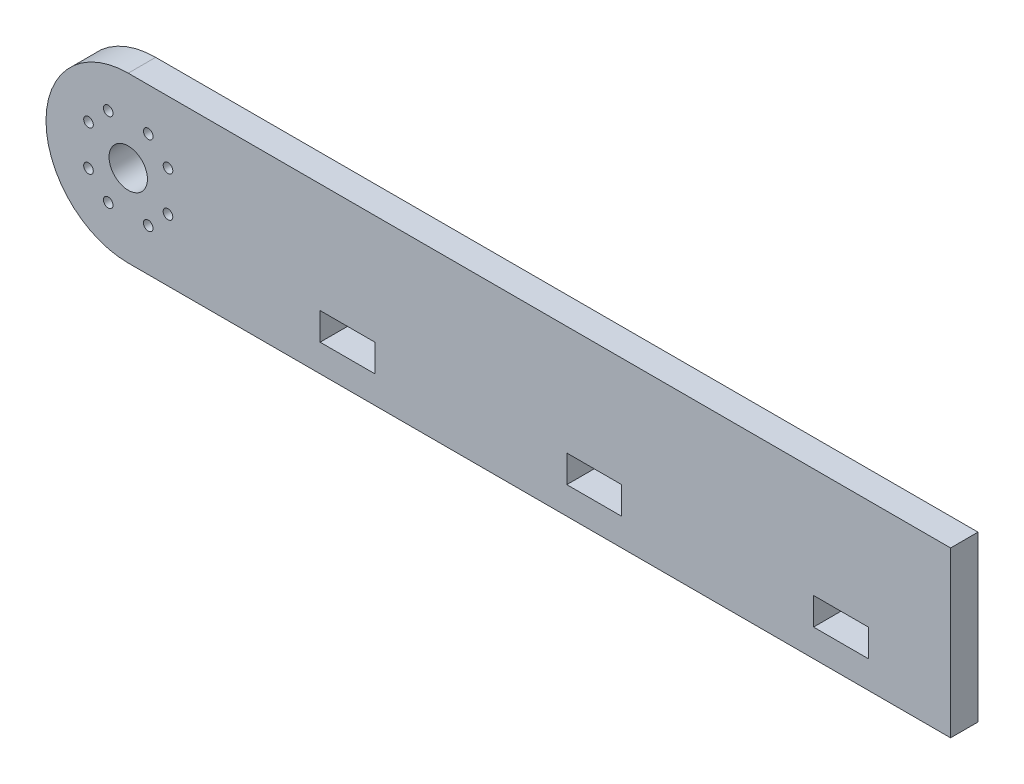
SolidWorks part; units mm, degrees
ref_plane "Plan de face" through (0, 0, 0) normal (0, 0, 1) x (1, 0, 0)
ref_plane "Plan de dessus" through (0, 0, 0) normal (0, 1, 0) x (1, 0, 0)
ref_plane "Plan de droite" through (0, 0, 0) normal (1, 0, 0) x (0, 0, -1)
sketch "Esquisse1" plane through (0, 0, 0) normal (0, 0, 1) x (1, 0, 0)
  line L0 (0, 0) -> (179.4908, 0) construction
  line L2 (0, 15) -> (150, 15)
  line L3 (0, -15) -> (150, -15)
  line L4 (150, 15) -> (150, -15)
  line L5 (35, -5) -> (45, -5)
  line L6 (35, -5) -> (35, -10)
  line L7 (35, -10) -> (45, -10)
  line L8 (45, -5) -> (45, -10)
  line L9 (80, -5) -> (90, -5)
  line L10 (80, -5) -> (80, -10)
  line L11 (80, -10) -> (90, -10)
  line L12 (90, -5) -> (90, -10)
  line L13 (125, -5) -> (135, -5)
  line L14 (125, -5) -> (125, -10)
  line L15 (125, -10) -> (135, -10)
  line L16 (135, -5) -> (135, -10)
  arc A0 (0, 15) -> (0, -15) centre (0, 0) ccw
  line B0 (0, 0) -> (7.25, 0) construction
  line B1 (7.25, 0) -> (7.25, 3.65) construction
  circle B2 centre (0, 0) radius 3.5
  circle B3 centre (7.25, 3.65) radius 0.875
  circle B4 centre (7.25, -3.65) radius 0.875
  circle B5 centre (7.25, -3.65) radius 0.875
  circle B6 centre (3.65, -7.25) radius 0.875
  circle B7 centre (-3.65, -7.25) radius 0.875
  circle B8 centre (-7.25, -3.65) radius 0.875
  circle B9 centre (-7.25, 3.65) radius 0.875
  circle B10 centre (-3.65, 7.25) radius 0.875
  circle B11 centre (3.65, 7.25) radius 0.875
  dimension "D1" = 30
  dimension "D8" = 5
  dimension "D2" = 150
  dimension "D3" = 5
  dimension "D4" = 10
  dimension "D5" = 35
  dimension "D6" = 35
  dimension "D7" = 35
sketch_block_instance "Bloc1-1"
sketch_block "Bloc1" parameters "D3"=1.75, "D1"=7.25, "D2"=3.65
extrude "Boss.-Extru.1" add sketch "Esquisse1" along normal blind 5 contours B2 L6 L5 L8 L10 L9 L12 L14 L13 L16 L4 L2 A0 L3 L15 L11 L7 B9 B8 B4 B3 B6 B7 B10 B11 region at (69.419, 0.2422, 0)
